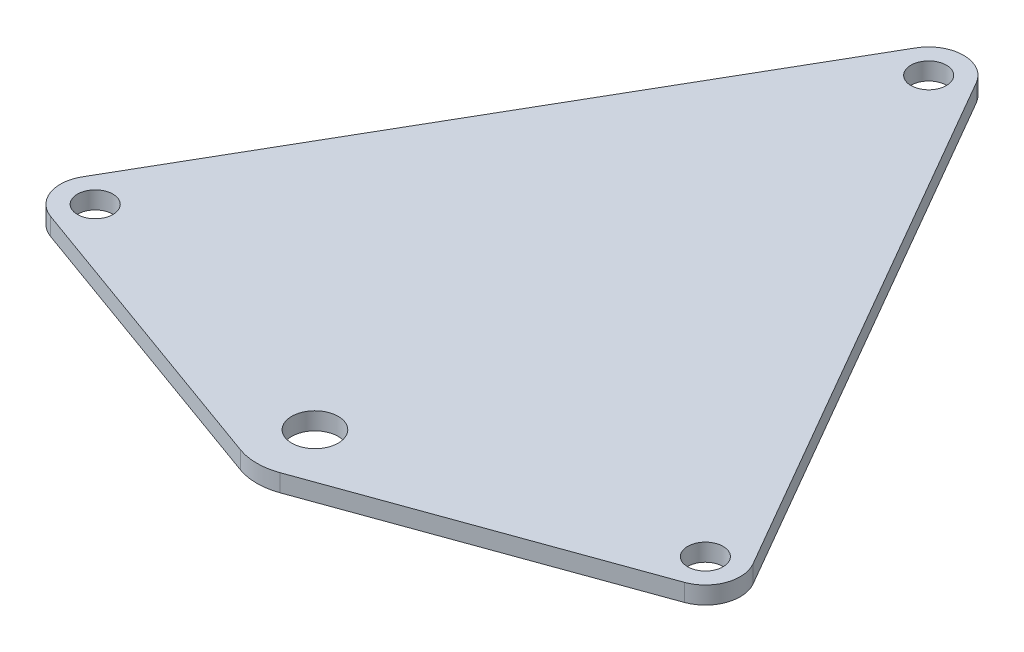
SolidWorks part; units mm, degrees
ref_plane "Front Plane" through (0, 0, 0) normal (0, 0, 1) x (1, 0, 0)
ref_plane "Top Plane" through (0, 0, 0) normal (0, 1, 0) x (1, 0, 0)
ref_plane "Right Plane" through (0, 0, 0) normal (1, 0, 0) x (0, 0, -1)
sketch "Sketch1" plane through (0, 0, 0) normal (0, 1, 0) x (1, 0, 0)
  line L0 (0, 60.6218) -> (-52.5, -30.3109) construction
  line L1 (-52.5, -30.3109) -> (52.5, -30.3109) construction
  line L2 (52.5, -30.3109) -> (0, 60.6218) construction
  line L3 (-5.1962, 63.6218) -> (-57.6962, -27.3109)
  line L4 (-52.5, -36.3109) -> (52.5, -36.3109)
  line L5 (5.1962, 63.6218) -> (57.6962, -27.3109)
  line L6 (0, 60.6218) -> (0, 0) construction
  line L7 (0, 0) -> (-52.5, -30.3109) construction
  line L8 (0, 0) -> (52.5, -30.3109) construction
  line L9 (0, 0) -> (0, -45) construction
  line L10 (-54.5363, -35.9548) -> (-3.3938, -54.4065)
  line L11 (3.3938, -54.4065) -> (54.5363, -35.9548)
  line L12 (-19.1038, 57.533) -> (-6.1134, 50.033) construction
  line L13 (-40.2731, -45.3109) -> (-40.2731, -30.3109) construction
  circle A0 centre (0, 60.6218) radius 6 construction
  circle A1 centre (52.5, -30.3109) radius 6 construction
  circle A2 centre (-52.5, -30.3109) radius 6 construction
  arc A3 (-52.5, -36.3109) -> (-57.6962, -27.3109) centre (-52.5, -30.3109) cw
  arc A4 (57.6962, -27.3109) -> (52.5, -36.3109) centre (52.5, -30.3109) cw
  arc A5 (5.1962, 63.6218) -> (-5.1962, 63.6218) centre (0, 60.6218) ccw
  circle A6 centre (0, 60.6218) radius 3.05
  circle A7 centre (52.5, -30.3109) radius 3.05
  circle A8 centre (-52.5, -30.3109) radius 3.05
  circle A9 centre (0, -45) radius 10 construction
  arc A10 (-3.3938, -54.4065) -> (3.3938, -54.4065) centre (0, -45) ccw
  circle A11 centre (0, -45) radius 4
  arc A12 (0, 60.6218) -> (-29.9926, -52.6825) centre (0, 0) ccw construction
  circle A13 centre (-19.1038, 57.533) radius 6 construction
  circle A14 centre (-40.2731, -45.3109) radius 6 construction
  dimension "D2" = 12
  dimension "D3" = 6.1
  dimension "D4" = 20
  dimension "D6" = 8
  dimension "D7" = 12
  dimension "D1" = 105
  dimension "D5" = 45
  dimension "D8" = 15
extrude "Boss-Extrude1" add sketch "Sketch1" along normal blind 3 contours L5 A5 L3 A3 L4 A4 A8 A7 A6 | L10 A10 L11 A4 L4 A3 A11 region at (0, 0, 0) region at (0, 0, 37.4181)
